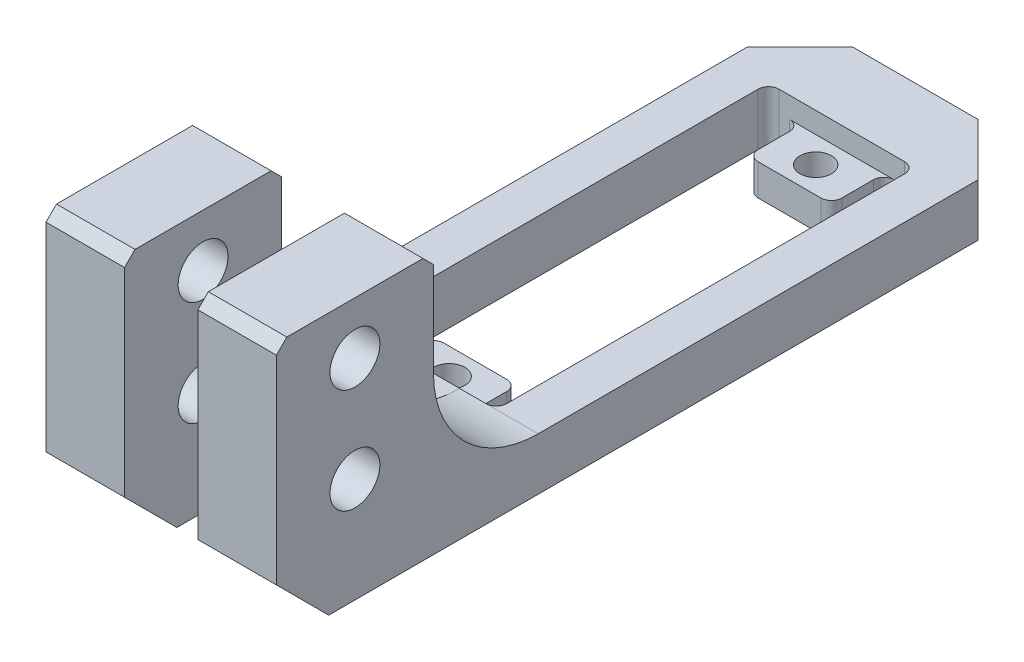
SolidWorks part; units mm, degrees
ref_plane "Front Plane" through (0, 0, 0) normal (0, 0, 1) x (1, 0, 0)
ref_plane "Top Plane" through (0, 0, 0) normal (0, 1, 0) x (1, 0, 0)
ref_plane "Right Plane" through (0, 0, 0) normal (1, 0, 0) x (0, 0, -1)
sketch "Sketch1" plane through (0, 0, 0) normal (0, 1, 0) x (1, 0, 0)
  line L1 (-11, -36) -> (11, -36)
  line L2 (-11, -36) -> (-11, 36)
  line L3 (-11, 36) -> (11, 36)
  line L4 (11, -36) -> (11, 36)
  line L5 (-11, -36) -> (11, 36) construction
  line L6 (-11, 36) -> (11, -36) construction
  point P0 (0, 0)
  dimension "D1" = 72
  dimension "D2" = 22
extrude "Boss-Extrude2" add sketch "Sketch1" along normal blind 5
sketch "Sketch2" plane through (0, 5, 0) normal (0, 1, 0) x (1, 0, 0)
  line L0 (11, 36) -> (-11, 36) construction
  line L1 (-7, -6) -> (7, -6)
  line L2 (-7, -6) -> (-7, 24)
  line L3 (-7, 24) -> (7, 24)
  line L4 (7, -6) -> (7, 24)
  line L5 (-7, -6) -> (7, 24) construction
  line L6 (-7, 24) -> (7, -6) construction
  point P0 (0, 9)
  dimension "D1" = 14
  dimension "D2" = 30
  dimension "D3" = 12
extrude "Cut-Extrude1" cut sketch "Sketch2" against normal through all
sketch "Sketch3" plane through (0, 5, 0) normal (0, 1, 0) x (1, 0, 0)
  line L1 (-7, 24) -> (-4, 24)
  line L2 (-7, 24) -> (-7, 29)
  line L3 (-7, 29) -> (-4, 29)
  line L4 (-4, 24) -> (-4, 29)
  line L5 (7, 24) -> (4, 24)
  line L6 (7, 24) -> (7, 29)
  line L7 (7, 29) -> (4, 29)
  line L8 (4, 24) -> (4, 29)
  line L9 (-7, -6) -> (-4, -6)
  line L10 (-7, -6) -> (-7, -11)
  line L11 (-7, -11) -> (-4, -11)
  line L12 (-4, -6) -> (-4, -11)
  line L13 (7, -6) -> (4, -6)
  line L14 (7, -6) -> (7, -11)
  line L15 (7, -11) -> (4, -11)
  line L16 (4, -6) -> (4, -11)
  point P20 (-4, -8.5)
  dimension "D1" = 3
  dimension "D2" = 5
extrude "Cut-Extrude2" cut sketch "Sketch3" against normal through all
sketch "Sketch4" plane through (0, 5, 0) normal (0, 1, 0) x (1, 0, 0)
  line L0 (-4, -6) -> (4, -6) construction
  line L1 (4, 24) -> (-4, 24) construction
  circle A0 centre (0, 26.5) radius 1.5
  circle A1 centre (0, -8.5) radius 1.5
  dimension "D1" = 3
  dimension "D2" = 2.5
  dimension "D3" = 2.5
extrude "Cut-Extrude3" cut sketch "Sketch4" against normal through all
sketch "Sketch5" plane through (0, 5, 0) normal (0, 1, 0) x (1, 0, 0)
  line L1 (-11, -36) -> (-3.5, -36)
  line L2 (-11, -36) -> (-11, -21)
  line L3 (-11, -21) -> (-3.5, -21)
  line L4 (-3.5, -36) -> (-3.5, -21)
  dimension "D1" = 15
  dimension "D2" = 7.5
extrude "Boss-Extrude3" add sketch "Sketch5" along normal blind 20
mirror "Mirror1" about plane through (0, 0, 0) normal (1, 0, 0) of "Boss-Extrude3"
chamfer "Chamfer2" distance 5 angle 45 1 edges at (0, 0, 36)
sketch "Sketch6" plane through (0, 5, 0) normal (0, 1, 0) x (1, 0, 0)
  line L0 (3.5, -36) -> (3.5, -21) construction
  line L1 (-3.5, -36) -> (3.5, -36)
  line L2 (-3.5, -36) -> (-3.5, -21)
  line L3 (-3.5, -21) -> (3.5, -21)
  line L4 (3.5, -36) -> (3.5, -21)
  dimension "D1" = 15
extrude "Cut-Extrude4" cut sketch "Sketch6" against normal through all
sketch "Sketch7" plane through (0, 5, 0) normal (0, 1, 0) x (1, 0, 0)
  line L1 (-4, 29) -> (4, 29)
  line L2 (-4, 29) -> (-4, 24)
  line L3 (-4, 24) -> (4, 24)
  line L4 (4, 29) -> (4, 24)
  line L5 (-4, -6) -> (4, -6)
  line L6 (-4, -6) -> (-4, -11)
  line L7 (-4, -11) -> (4, -11)
  line L8 (4, -6) -> (4, -11)
extrude "Cut-Extrude5" cut sketch "Sketch7" against normal blind 2
chamfer "Chamfer6" distance 5 angle 45 2 edges at (-11, 2.5, -36) (11, 2.5, -36)
fillet "Fillet3" radius 1 12 edges at (7, 2.5, -29) (4, 1.5, -29) (4, 1.5, -24) (-4, 1.5, -24) (-4, 1.5, -29) (-7, 2.5, -29) (-4, 1.5, 11) (-7, 2.5, 11) (7, 2.5, 11) (4, 1.5, 11) (-4, 1.5, 6) (4, 1.5, 6)
fillet "Fillet6" radius 10 2 edges at (7.25, 5, 21) (-7.25, 5, 21)
sketch "Sketch9" plane through (-11, 0, 0) normal (-1, 0, 0) x (0, 0, 1)
  line L1 (21, 25) -> (36, 25) construction
  circle A0 centre (28.5, 20) radius 2.3813
  circle A1 centre (28.5, 10) radius 2.3813
  point P7 (28.5, 25)
  dimension "D1" = 4.7625
  dimension "D2" = 10
  dimension "D3" = 5
extrude "Cut-Extrude6" cut sketch "Sketch9" against normal through all
chamfer "Chamfer8" distance 1 angle 45 4 edges at (7.25, 25, 36) (-7.25, 25, 36) (7.25, 25, 21) (-7.25, 25, 21)
